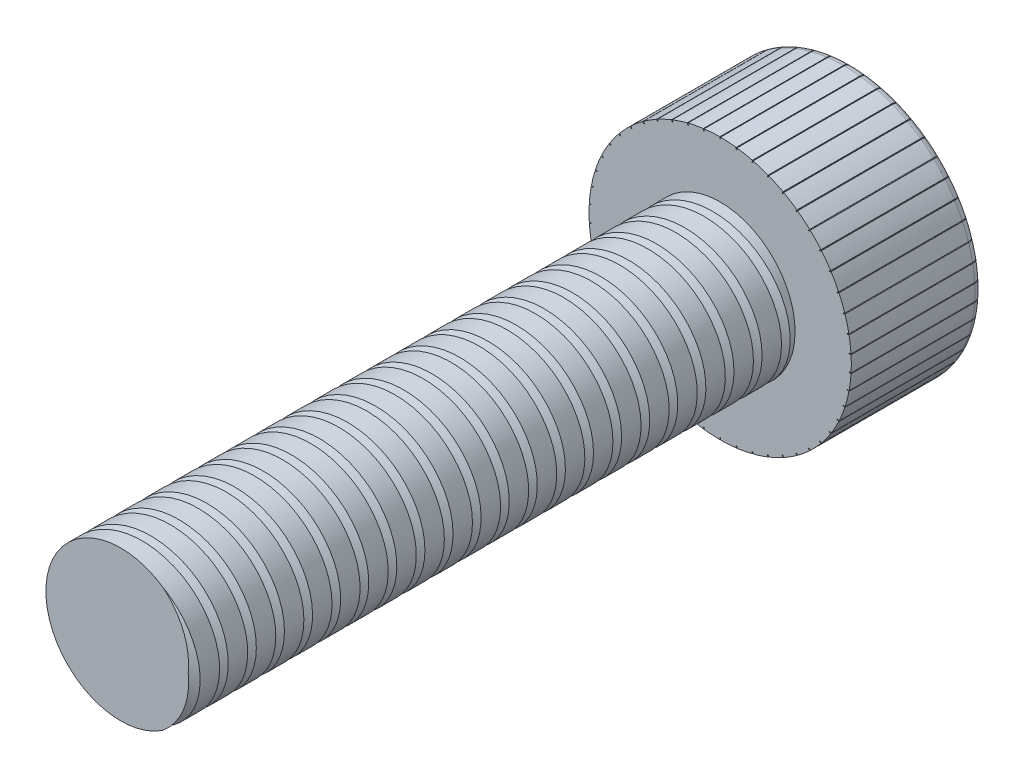
SolidWorks part; units mm, degrees
ref_plane "Front Plane" through (0, 0, 0) normal (0, 0, 1) x (1, 0, 0)
ref_plane "Top Plane" through (0, 0, 0) normal (0, 1, 0) x (1, 0, 0)
ref_plane "Right Plane" through (0, 0, 0) normal (1, 0, 0) x (0, 0, -1)
sketch "Sketch1" plane through (0, 0, 0) normal (0, 0, 1) x (1, 0, 0)
  circle A0 centre (0, 0) radius 3.5
extrude "Boss-Extrude1" add sketch "Sketch1" along normal blind 3.5
sketch "Sketch2" plane through (0, 0, 3.5) normal (0, 0, 1) x (1, 0, 0)
  circle A0 centre (0, 0) radius 2
extrude "Boss-Extrude2" add sketch "Sketch2" along normal blind 16
sketch "Sketch3" plane through (0, 0, 0) normal (0, 0, -1) x (-1, 0, 0)
  line L1 (-1.2556, -1.1931) -> (0.4054, -1.6839)
  line L2 (0.4054, -1.6839) -> (1.661, -0.4909)
  line L3 (1.661, -0.4909) -> (1.2556, 1.1931)
  line L4 (1.2556, 1.1931) -> (-0.4054, 1.6839)
  line L5 (-0.4054, 1.6839) -> (-1.661, 0.4909)
  line L6 (-1.661, 0.4909) -> (-1.2556, -1.1931)
  circle A0 centre (0, 0) radius 1.5 construction
extrude "Cut-Extrude1" cut sketch "Sketch3" against normal blind 2.3
fillet "Fillet1" radius 0.2 1 edges at (3.5, 0, 0)
sketch "Sketch4" plane through (0, 0, 0) normal (0, 0, -1) x (-1, 0, 0)
  line L1 (-0.01, 4) -> (0.01, 4)
  line L2 (-0.01, 4) -> (-0.01, 3.45)
  line L3 (-0.01, 3.45) -> (0.01, 3.45)
  line L4 (0.01, 4) -> (0.01, 3.45)
extrude "Cut-Extrude2" cut sketch "Sketch4" against normal blind 4
ref_axis "Axis1" through (0, 0, 0) along (0, 0, -1)
pattern_circular "CirPattern1" count 50 over 360 about axis through (0, 0, 0) along (0, 0, -1) of "Cut-Extrude2"
sketch "Sketch7" plane through (0, 0, 19.5) normal (0, 0, 1) x (1, 0, 0)
  circle A0 centre (0, 0) radius 2
curve "Helix/Spiral1" pitch 0.75 height 16 radius 2 centre (0, 0, 19.5) axis (0, 0, -1) start towards (1, 0, 0)
sketch "Sketch12" plane through (0, 0, 0) normal (0, 1, 0) x (1, 0, 0)
  line L1 (1.8, -19.5) -> (2.1, -19.6732)
  line L2 (2.1, -19.6732) -> (2.1, -19.3268)
  line L3 (2.1, -19.3268) -> (1.8, -19.5)
  circle A0 centre (2, -19.5) radius 0.1 construction
sweep "Cut-Sweep1" cut profiles "Sketch12" path "Helix/Spiral1" align with end faces yes
